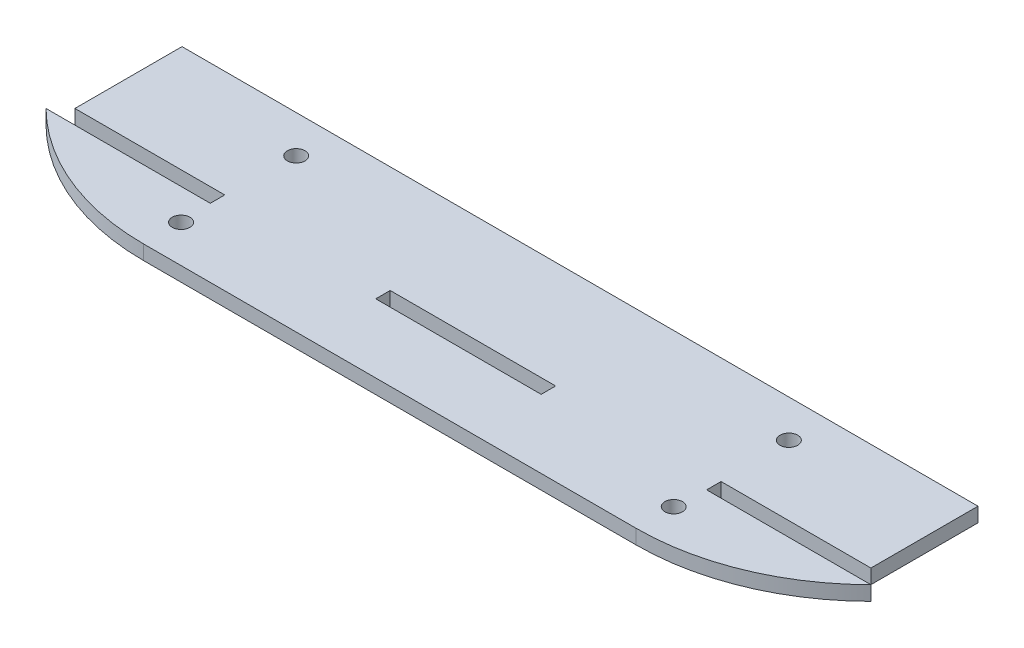
SolidWorks part; units mm, degrees
ref_plane "Ön Düzlem" through (0, 0, 0) normal (0, 0, 1) x (1, 0, 0)
ref_plane "Üst Düzlem" through (0, 0, 0) normal (0, 1, 0) x (1, 0, 0)
ref_plane "Sağ Düzlem" through (0, 0, 0) normal (1, 0, 0) x (0, 0, -1)
sketch "Sketch1" plane through (0, 0, 0) normal (0, 1, 0) x (1, 0, 0)
  line L0 (46.3452, 15.5) -> (74.3252, 15.5)
  line L1 (-46, 0) -> (46, 0)
  line L3 (-46.3452, 15.5) -> (-74.3252, 15.5)
  line L4 (-77.0252, 12.8) -> (-46.3452, 12.8)
  line L6 (77.0252, 12.8) -> (46.3452, 12.8)
  line L7 (-46.3452, 12.8) -> (-46.3452, 15.5)
  line L9 (46.3452, 15.5) -> (46.3452, 12.8)
  line L10 (-15.4484, 15.5) -> (15.4484, 15.5)
  line L12 (15.4484, 15.5) -> (15.4484, 12.8)
  line L13 (-15.4484, 15.5) -> (-15.4484, 12.8)
  line L15 (-74.3252, 15.5) -> (-74.3252, 35.5)
  line L16 (-15.4484, 12.8) -> (15.4484, 12.8)
  line L17 (-74.3252, 35.5) -> (74.3252, 35.5)
  line L18 (74.3252, 35.5) -> (74.3252, 15.5)
  arc A0 (-77.0252, 12.8) -> (-46, 0) centre (-46, 44) ccw
  arc A1 (46, 0) -> (77.0252, 12.8) centre (46, 44) ccw
  circle A2 centre (46, 28.5) radius 1.65
  circle A3 centre (46, 7) radius 1.65
  circle A4 centre (-46, 7) radius 1.65
  circle A5 centre (-46, 28.5) radius 1.65
extrude "Boss-Extrude1" add sketch "Sketch1" along normal blind 2.7
